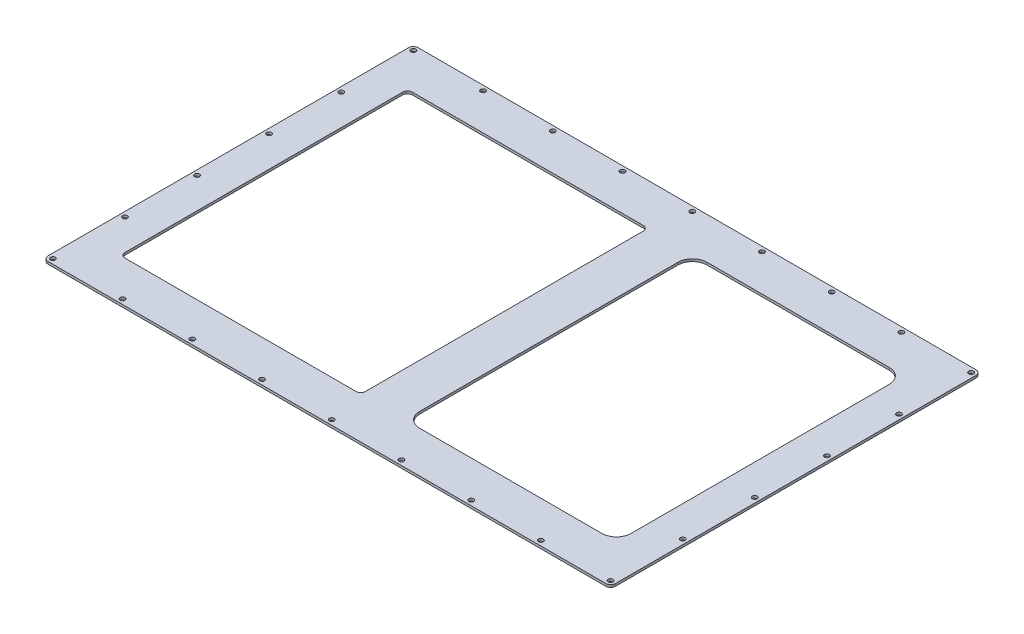
SolidWorks part; units mm, degrees
ref_plane "Спереди" through (0, 0, 0) normal (0, 0, 1) x (1, 0, 0)
ref_plane "Сверху" through (0, 0, 0) normal (0, 1, 0) x (1, 0, 0)
ref_plane "Справа" through (0, 0, 0) normal (1, 0, 0) x (0, 0, -1)
sketch "Эскиз1" plane through (0, 0, 0) normal (0, 1, 0) x (1, 0, 0)
  line L1 (-582.5, -380) -> (582.5, -380)
  line L2 (-582.5, -380) -> (-582.5, 380)
  line L3 (-582.5, 380) -> (582.5, 380)
  line L4 (582.5, -380) -> (582.5, 380)
  line L5 (0, 380) -> (0, -380) construction
  line L6 (-582.5, 0) -> (582.5, 0) construction
  line L7 (-509.5, 295) -> (-15.5, 295)
  line L8 (-509.5, 295) -> (-509.5, -295)
  line L9 (-509.5, -295) -> (-15.5, -295)
  line L10 (-15.5, 295) -> (-15.5, -295)
  line L11 (75.5, 295) -> (509.5, 295)
  line L12 (75.5, 295) -> (75.5, -295)
  line L13 (75.5, -295) -> (509.5, -295)
  line L14 (509.5, 295) -> (509.5, -295)
  point P0 (0, 0)
  dimension "D1" = 1165
  dimension "D2" = 760
  dimension "D3" = 73
  dimension "D4" = 85
  dimension "D5" = 85
  dimension "D6" = 494
  dimension "D7" = 73
  dimension "D8" = 434
extrude "Бобышка-Вытянуть1" add sketch "Эскиз1" along normal mid plane 5
fillet "Скругление1" radius 10 8 edges at (582.5, 0, 380) (-582.5, 0, 380) (582.5, 0, -380) (-582.5, 0, -380) (-15.5, 0, 295) (-509.5, 0, 295) (-15.5, 0, -295) (-509.5, 0, -295)
fillet "Скругление2" radius 30 4 edges at (75.5, 0, 295) (509.5, 0, 295) (509.5, 0, -295) (75.5, 0, -295)
sketch "Эскиз2" plane through (0, 2.5, 0) normal (0, 1, 0) x (1, 0, 0)
  circle A0 centre (-572.5, -370) radius 5
  arc A1 (-582.5, -370) -> (-572.5, -380) centre (-572.5, -370) ccw construction
  circle A2 centre (-572.5, 370) radius 5 construction
  arc A3 (-572.5, 380) -> (-582.5, 370) centre (-572.5, 370) ccw construction
  circle A4 centre (572.5, -370) radius 5 construction
  arc A5 (572.5, -380) -> (582.5, -370) centre (572.5, -370) ccw construction
  point P11 (-572.5, 370)
  point P17 (572.5, -370)
  dimension "D1" = 10
extrude "Вырез-Вытянуть1" cut sketch "Эскиз2" against normal through all
ref_plane "Плоскость1" through (30, 0, 0) normal (-1, 0, 0) x (0, 0, 1)
pattern_linear "Линейный массив1" count 6 spacing 148 along (0, 0, -1) count 9 spacing 143.125 along (1, 0, 0) skipping (1, 1), (1, 2), (1, 3), (1, 4), (1, 5), (1, 6), (1, 7), (2, 1), (2, 2), (2, 3), (2, 4), (2, 5), (2, 6), (2, 7), (3, 1), (3, 2), (3, 3), (3, 4), (3, 5), (3, 6), (3, 7), (4, 1), (4, 2), (4, 3), (4, 4) of "Вырез-Вытянуть1"
